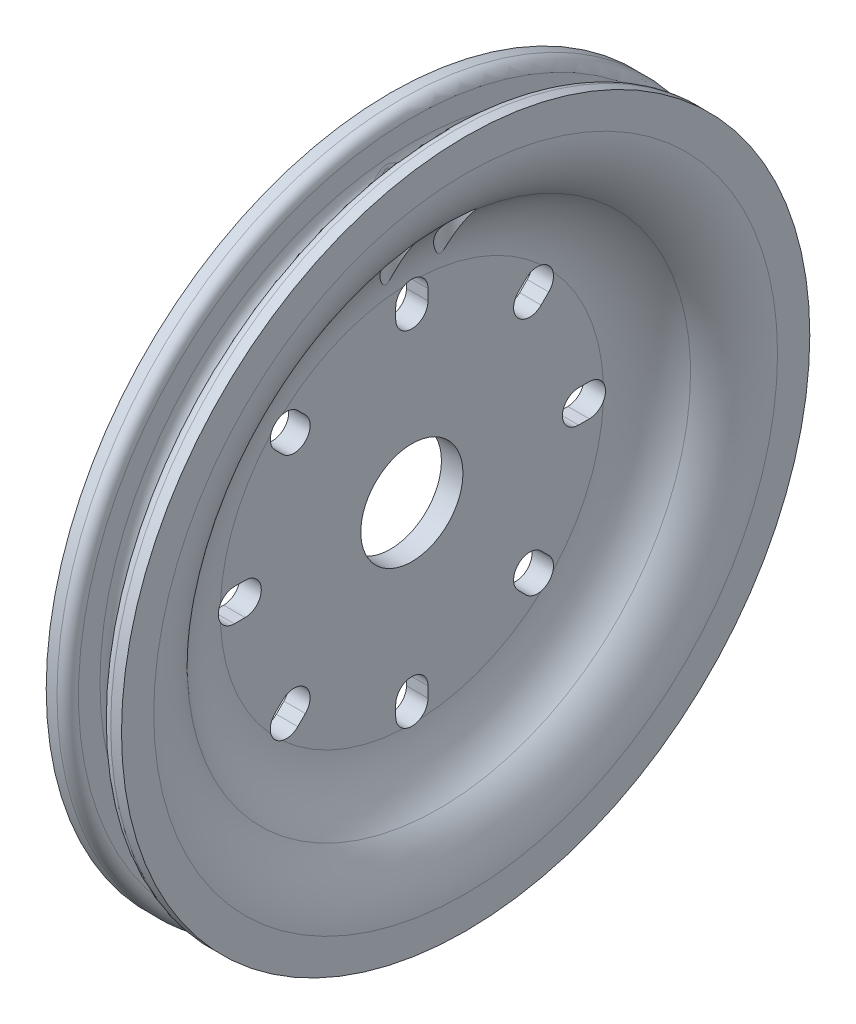
SolidWorks part; units mm, degrees
material "ABS"
ref_plane "Plan de face" through (0, 0, 0) normal (0, 0, 1) x (1, 0, 0)
ref_plane "Plan de dessus" through (0, 0, 0) normal (0, 1, 0) x (1, 0, 0)
ref_plane "Plan de droite" through (0, 0, 0) normal (1, 0, 0) x (0, 0, -1)
sketch "Esquisse1" plane through (0, 0, 0) normal (0, 0, 1) x (1, 0, 0)
  line L0 (1, 0) -> (-1, 0) construction
  line L1 (-1, 32) -> (1, 32)
  line L2 (-1, 32) -> (-1, 4.75)
  line L4 (1, 17.8197) -> (1, 4.75)
  line L5 (1, 32) -> (1, 29)
  line L6 (4, 29) -> (4, 32)
  line L7 (4, 32) -> (6, 32)
  line L8 (6, 32) -> (6, 29)
  line L9 (-1, 4.75) -> (1, 4.75)
  arc A0 (1, 29) -> (4, 29) centre (2.5, 29) ccw
  arc A1 (6, 29) -> (3.5, 23.4098) centre (-1.5, 29) cw
  arc A2 (3.5, 23.4098) -> (1, 17.8197) centre (8.5, 17.8197) ccw
  point P3 (2.5, 27.5)
  dimension "D1" = 3
  dimension "D5" = 55
  dimension "D8" = 7.5
  dimension "D2" = 2
  dimension "D3" = 2
  dimension "D4" = 3
  dimension "D6" = 9.5
  dimension "D7" = 64
revolve "Révolution1" add sketch "Esquisse1" angle 360 about L0
fillet "Congé1" radius 1 2 edges at (4, 0, -32) (1, 0, -32)
sketch "Esquisse2" plane through (0, 0, 0) normal (0, 1, 0) x (1, 0, 0)
  line L0 (-1, 0) -> (6, 0) construction
  line L1 (-1, 32) -> (-1, -32) construction
  line L2 (6, -29) -> (6, 29) construction
  circle A0 centre (2.5, 2.5) radius 1.4
  circle A1 centre (2.5, -2.5) radius 1.4
  point P8 (2.5, 0)
  dimension "D1" = 5
  dimension "D2" = 2.8
extrude "Enlèv. mat.-Extru.1" cut sketch "Esquisse2" along normal through all
fillet "Congé2" radius 1 2 edges at (3.1874, 27.6371, -1.2804) (3.066, 27.3508, 3.7805)
sketch "Esquisse3" plane through (-1, 0, 0) normal (-1, 0, 0) x (0, 0, 1)
  line L0 (0, 16.5) -> (0, 15.5) construction
  line L1 (1.5, 16.5) -> (1.5, 15.5)
  line L2 (-1.5, 16.5) -> (-1.5, 15.5)
  arc A0 (1.5, 16.5) -> (-1.5, 16.5) centre (0, 16.5) ccw
  arc A1 (-1.5, 15.5) -> (1.5, 15.5) centre (0, 15.5) ccw
  point P3 (0, 16)
  dimension "D1" = 16
  dimension "D2" = 1
  dimension "D3" = 3
extrude "Enlèv. mat.-Extru.2" cut sketch "Esquisse3" against normal through all
pattern_circular "Répétition circulaire1" count 8 over 360 about axis through (-1, 0, 0) along (1, 0, 0) of "Enlèv. mat.-Extru.2"
sketch "Esquisse4" plane through (-1, 0, 0) normal (-1, 0, 0) x (0, 0, 1)
  circle A1 centre (0, 0) radius 32
  circle A2 centre (0, 0) radius 32
  dimension "D1" = 0
extrude "Boss.-Extru.1" [suppressed] add sketch "Esquisse4" against normal blind 0.2
